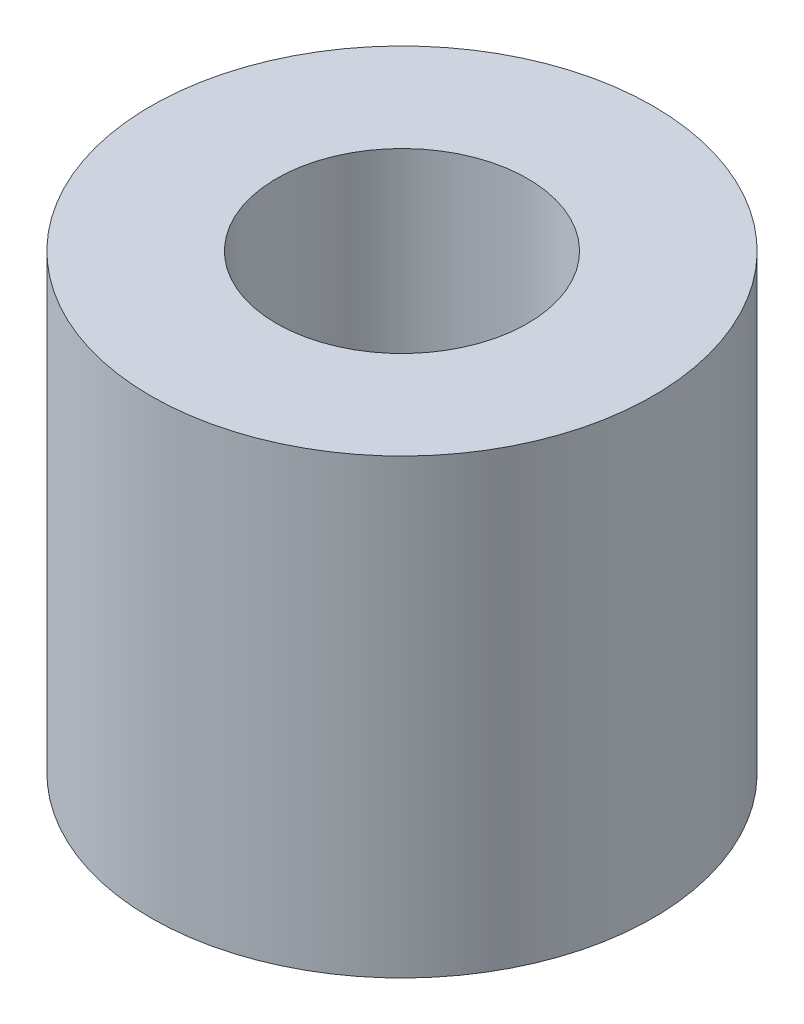
SolidWorks part; units mm, degrees
ref_plane "Front Plane" through (0, 0, 0) normal (0, 0, 1) x (1, 0, 0)
ref_plane "Top Plane" through (0, 0, 0) normal (0, 1, 0) x (1, 0, 0)
ref_plane "Right Plane" through (0, 0, 0) normal (1, 0, 0) x (0, 0, -1)
sketch "Sketch1" plane through (0, 0, 0) normal (0, 1, 0) x (1, 0, 0)
  circle A0 centre (0, 0) radius 5
  circle A1 centre (0, 0) radius 2.5
  dimension "D1" = 5
  dimension "D2" = 10
extrude "Boss-Extrude1" add sketch "Sketch1" along normal blind 9
